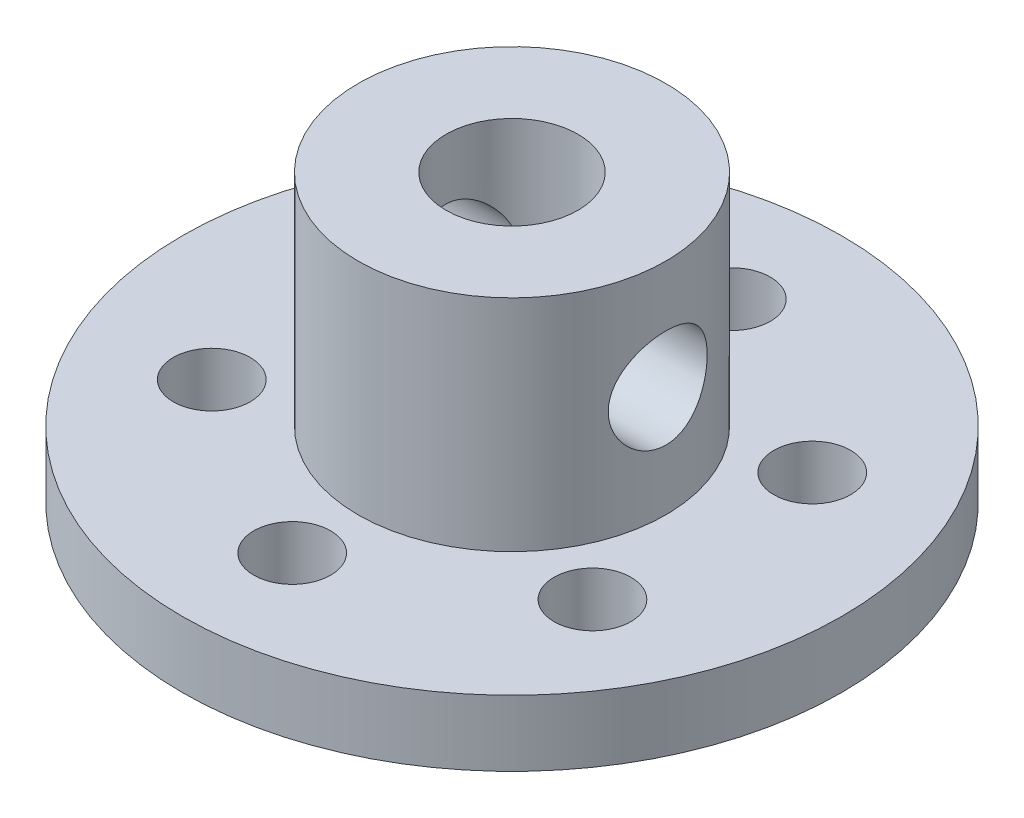
SolidWorks part; units mm, degrees
ref_plane "Front Plane" through (0, 0, 0) normal (0, 0, 1) x (1, 0, 0)
ref_plane "Top Plane" through (0, 0, 0) normal (0, 1, 0) x (1, 0, 0)
ref_plane "Right Plane" through (0, 0, 0) normal (1, 0, 0) x (0, 0, -1)
sketch "Sketch1" plane through (0, 0, 0) normal (0, 1, 0) x (1, 0, 0)
  circle A0 centre (0, 0) radius 15
  circle A1 centre (0, 0) radius 7
  circle A2 centre (0, 0) radius 3
  circle A3 centre (0, 10) radius 1.75
  circle A4 centre (8.6603, 5) radius 1.75
  circle A5 centre (8.6603, -5) radius 1.75
  circle A6 centre (0, -10) radius 1.75
  circle A7 centre (-8.6603, -5) radius 1.75
  circle A8 centre (-8.6603, 5) radius 1.75
  point P19 (0, 0)
  dimension "D1" = 30
  dimension "D2" = 14
  dimension "D3" = 6
  dimension "D4" = 3.5
  dimension "D5" = 10
  dimension "D6" = 6
extrude "Boss-Extrude1" add sketch "Sketch1" along normal blind 3 contours A0 A8 A7 A6 A5 A4 A3 A1 region at (-14.5757, 0, 0)
extrude "Boss-Extrude2" add sketch "Sketch1<3>" along normal blind 13 contours A1 A2 region at (-6.802, 0, 0)
sketch "Sketch1<3>" plane through (0, 0, 0) normal (0, 1, 0) x (1, 0, 0) same geometry as "Sketch1"
sketch "Sketch2" plane through (0, 0, 0) normal (1, 0, 0) x (0, 0, -1)
  line L0 (7, 13) -> (-7, 13) construction
  circle A0 centre (0, 8) radius 2.25
  dimension "D1" = 4.5
  dimension "D2" = 5
extrude "Cut-Extrude1" cut sketch "Sketch2" against normal through all both and the other way through all
